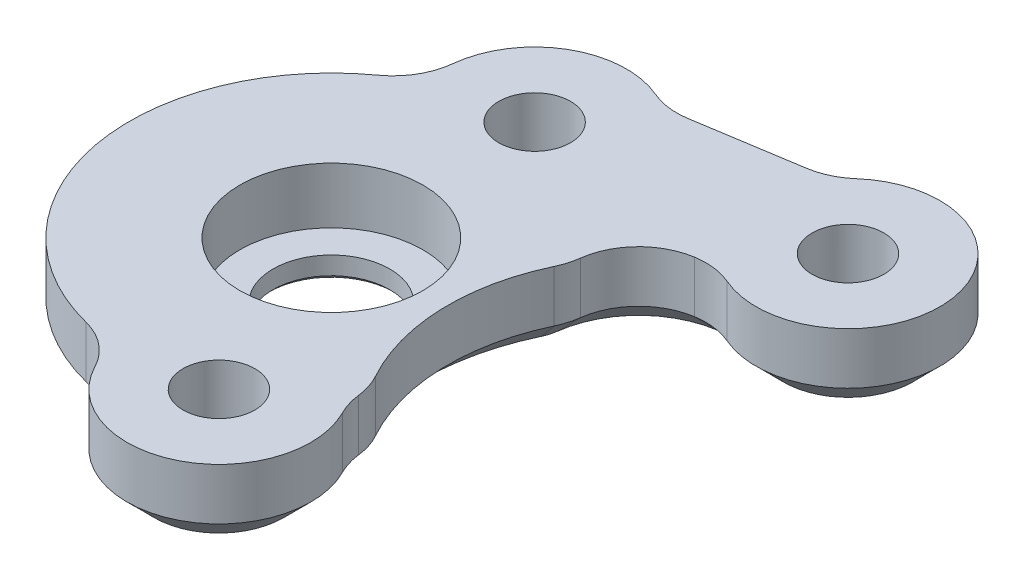
SolidWorks part; units mm, degrees
ref_plane "Front Plane" through (0, 0, 0) normal (0, 0, 1) x (1, 0, 0)
ref_plane "Top Plane" through (0, 0, 0) normal (0, 1, 0) x (1, 0, 0)
ref_plane "Right Plane" through (0, 0, 0) normal (1, 0, 0) x (0, 0, -1)
sketch "Sketch1" plane through (0, 0, 0) normal (0, 1, 0) x (1, 0, 0)
  circle A0 centre (0, 0) radius 9
  circle A1 centre (0, 0) radius 4.08
  dimension "D1" = 18
  dimension "D2" = 8.16
extrude "Boss-Extrude1" add sketch "Sketch1" along normal blind 3.5
sketch "Sketch2" plane through (0, 3.5, 0) normal (0, 1, 0) x (1, 0, 0)
  circle A0 centre (3.3433, -8.356) radius 1.6
  circle A1 centre (0.0612, 8.9998) radius 1.6
  circle A2 centre (3.3433, -8.356) radius 4.1
  circle A3 centre (0.0612, 8.9998) radius 4.1
  dimension "D1" = 2.5
extrude "Boss-Extrude2" add sketch "Sketch2" against normal blind 3.5
sketch "Sketch6" plane through (0, 0, 0) normal (0, -1, 0) x (-1, 0, 0)
  circle A0 centre (-14.2, 0) radius 9
  dimension "D1" = 18
  dimension "D2" = 14.2
extrude "Cut-Extrude2" cut sketch "Sketch6" against normal through all
sketch "Sketch3" plane through (0, 0, 0) normal (0, -1, 0) x (-1, 0, 0)
  circle A0 centre (-0.0612, 8.9998) radius 1.6
  arc A1 (-4.7701, -7.6319) -> (-1.8108, -8.8159) centre (0, 0) ccw construction
  arc A2 (1.5334, 8.8684) -> (-1.6538, 8.8467) centre (0, 0) ccw construction
  circle A4 centre (-3.3433, -8.356) radius 1.6
extrude "Cut-Extrude1" cut sketch "Sketch3" against normal blind 3.5
sketch "Sketch4" plane through (0, 0, 0) normal (0, -1, 0) x (-1, 0, 0)
  line L0 (-0.0612, 8.9998) -> (-12.1263, 10.9048) construction
  line L1 (-2.3537, 12.3989) -> (-8.898, 13.4322)
  line L3 (-5.8131, 6.8708) -> (-9.8338, 7.5057)
  circle A0 centre (-12.1263, 10.9048) radius 1.6
  arc A1 (-8.898, 13.4322) -> (-9.8338, 7.5057) centre (-12.1263, 10.9048) ccw
  arc A2 (-2.3537, 12.3989) -> (-4.047, 8.0388) centre (-0.0612, 8.9998) ccw
  arc A3 (-4.047, 8.0388) -> (-5.8131, 6.8708) centre (0, 0) ccw
  circle A5 centre (-12.1263, 10.9048) radius 4.1 construction
  point P4 (-12.1263, 10.9048)
  point P5 (-12.1263, 10.9048)
  point P8 (-7.2556, 11.7052)
  point P9 (-12.1263, 10.9048)
  point P10 (-8.0263, 10.9048)
  point P13 (-8.0263, 10.9048)
  point P17 (-8.0263, 10.9048)
  arc M5 (-4.047, 8.0388) -> (-7.1, 5.5308) centre (0, 0) ccw
  dimension "D2" = 3
  dimension "D1" = 2.5
extrude "Boss-Extrude3" add sketch "Sketch4" against normal blind 3.5 contours A0 M5 region at (9.8918, 0, -10.6162)
sketch "Sketch5" plane through (0, 0, 0) normal (0, -1, 0) x (-1, 0, 0)
  circle A0 centre (0, 0) radius 4.08
  circle A1 centre (0, 0) radius 2.6
  dimension "D1" = 5.2
  dimension "D2" = 8.16
extrude "Boss-Extrude4" add sketch "Sketch5" against normal blind 1
fillet "Fillet1" radius 3 7 edges at (-3.9373, 1.75, -8.0931) (-0.7102, 1.75, 8.9719) (9.8338, 1.75, -7.5057) (8.898, 1.75, -13.4322) (2.3537, 1.75, -12.3989) (7.1, 1.75, -5.5308) (7.1, 1.75, 5.5308)
fillet "Fillet9" radius 3 2 edges at (5.8131, 1.75, -6.8708) (6.7029, 1.75, 6.0059)
chamfer "倒角1" distance 1.2 angle 45 16 edges at (16.1761, 0, -11.5442) (8.7151, 0, -13.5234) (9.6878, 0, -7.3626) (5.6259, 0, -12.9156) (8.8438, 0, -7.3493) (2.4996, 0, -12.542) (7.1582, 0, -6.4755) (-2.0077, 0, -12.5396) (6.238, 0, -4.3017) (-4.406, 0, -8.2391) (5.2046, 0, 0.2865) (-8.8433, 0, 1.6723) (6.5641, 0, 4.9054) (-1.0932, 0, 9.279) (6.7966, 0, 5.9989) (5.2201, 0, 12.0012)
chamfer "倒角2" distance 0.2 angle 45 4 edges at (3.3433, 0, 9.956) (12.1263, 0, -12.5048) (0, 0, -2.6) (0.0612, 0, -7.3998)
equation "\"D2@Sketch6\"=5.2+\"D1@Sketch6\"/2"
